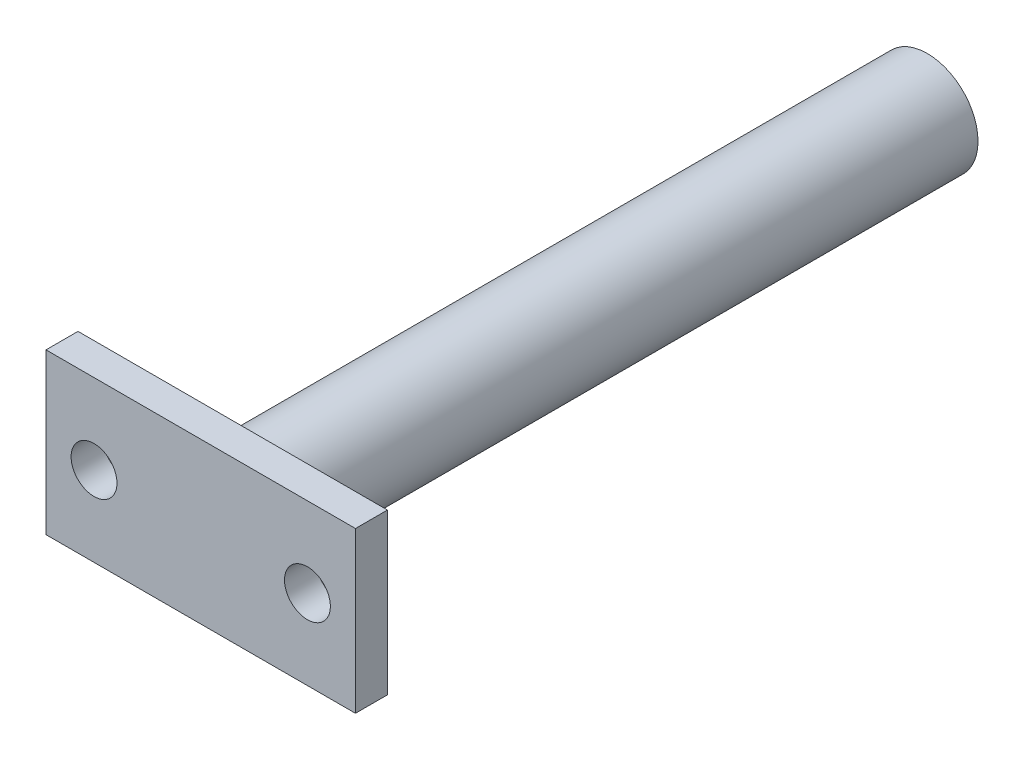
SolidWorks part; units mm, degrees
ref_plane "Front Plane" through (0, 0, 0) normal (0, 0, 1) x (1, 0, 0)
ref_plane "Top Plane" through (0, 0, 0) normal (0, 1, 0) x (1, 0, 0)
ref_plane "Right Plane" through (0, 0, 0) normal (1, 0, 0) x (0, 0, -1)
sketch "Sketch1" plane through (0, 0, 0) normal (0, 0, 1) x (1, 0, 0)
  line L0 (-28.1329, 0.594) -> (1.8671, 0.594)
  line L1 (-28.1329, 0.094) -> (1.8671, 0.094)
  line L2 (-28.1329, -0.4803) -> (-28.1329, 16.094)
  line L3 (-28.1329, 16.094) -> (1.8671, 16.094)
  line L4 (1.8671, -0.4803) -> (1.8671, 16.094)
  line L5 (1.3671, -0.4803) -> (1.3671, 15.594)
  line L6 (-27.6329, 15.594) -> (1.3671, 15.594)
  line L7 (-27.6329, -0.4803) -> (-27.6329, 15.594)
  circle A1 centre (-13.1404, 8.094) radius 4.75
  circle A4 centre (-3.1329, 8.094) radius 2.15
  circle A5 centre (-23.1329, 8.094) radius 2.15
  dimension "D5" = 9.5
  dimension "D6" = 0.5
extrude "Boss-Extrude1" add sketch "Sketch1" along normal blind 3 contours L7 L0 L5 L6 A5 A4 A1 region at (-27.3064, 8.094, 0)
extrude "Boss-Extrude2" add sketch "Sketch1<3>" against normal blind 65.1 and the other way up to surface (3 mm away) contours A1 region at (-13.1404, 8.094, 0) other way up to face at (-20.9829, 8.094, 3)
sketch "Sketch1<3>" plane through (0, 0, 0) normal (0, 0, 1) x (1, 0, 0) same geometry as "Sketch1"
